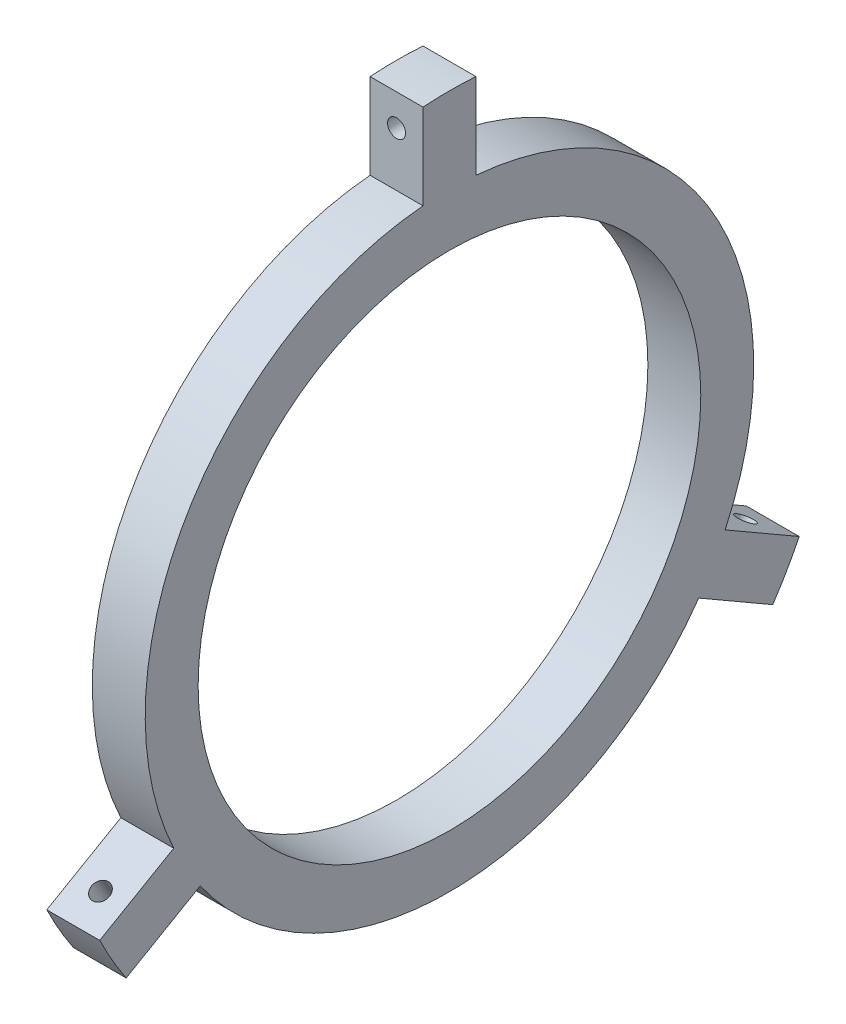
SolidWorks part; units mm, degrees
ref_plane "Plan de face" through (0, 0, 0) normal (0, 0, 1) x (1, 0, 0)
ref_plane "Plan de dessus" through (0, 0, 0) normal (0, 1, 0) x (1, 0, 0)
ref_plane "Plan de droite" through (0, 0, 0) normal (1, 0, 0) x (0, 0, -1)
sketch "Esquisse2" plane through (0, 0, 0) normal (0, 0, 1) x (1, 0, 0)
  line L0 (-5, 0) -> (5, 0)
  line L1 (5, 0) -> (5, 73.61)
  line L2 (5, 73.61) -> (-5, 73.61)
  line L3 (-5, 73.61) -> (-5, 0)
  dimension "D1" = 73.61
  dimension "D2" = 10
extrude "Boss.-Extru.1" add sketch "Esquisse2" along normal blind 5 and the other way blind 5
sketch "Esquisse3" plane through (5, 0, 0) normal (1, 0, 0) x (0, 0, -1)
  line L0 (0, 0) -> (0, 73.61) construction
  line L1 (-25.3992, 69.0892) -> (-25.3992, 83.5877)
  line L2 (-25.3992, 83.5877) -> (25.3992, 83.5877)
  line L3 (25.3992, 83.5877) -> (25.3992, 69.0892)
  line L4 (5, 75) -> (-5, 75) construction
  line L5 (-5, 0) -> (-5, 73.61) construction
  arc A0 (-25.3992, 69.0892) -> (25.3992, 69.0892) centre (0, 0) cw
  dimension "D1" = 73.61
  dimension "D2" = 30.3992
  dimension "D3" = 8.5877
extrude "Enlèv. mat.-Extru.1" cut sketch "Esquisse3" against normal through all
sketch "Esquisse5" plane through (0, 0, 0) normal (0, 1, 0) x (1, 0, 0)
  line L0 (0, 0) -> (7.3012, 0) construction
ref_plane "Plan3" through (0, 0, 0) normal (0, 0, -1) x (-1, 0, 0)
ref_plane "Plan4" through (0, 73.44, 0) normal (0, -1, 0) x (-1, 0, 0)
hole_wizard "Dégagement M31" positions "Esquisse6" profile "Esquisse7" hole size "M3" standard "ISO" end condition through all
sketch "Esquisse6" plane through (0, 0, -5) normal (0, 0, -1) x (-1, 0, 0)
  line L1 (0, 67.5) -> (5, 73.44) construction
  line L3 (0, 67.5) -> (-5, 73.44) construction
  point P35 (0, 67.5)
  dimension "D1" = 67.5
sketch "Esquisse7" plane through (0, 67.5, -5) normal (1, 0, 0) x (0, 1, 0)
  line L0 (0, 0) -> (0, 73.6009)
  line L1 (0, 73.6009) -> (1.7, 73.6009)
  line L2 (1.7, 73.6009) -> (1.7, 0)
  line L5 (1.7, 0) -> (0, 0)
  line L11 (0, -6.35) -> (0, 107.95) construction
  dimension "Diamètre du perçage jusqu'au prochain" = 3.4
  dimension "Profondeur du perçage jusqu'au prochain" = 73.6009
pattern_circular "Répétition circulaire1" count 3 over 360 about axis through (0, 0, 0) along (1, 0, 0) of "Boss.-Extru.1", "Enlèv. mat.-Extru.1", "Dégagement M31" reverse direction yes
ref_plane "Plan1" [suppressed] through (0, 0, 0) normal (0, 0.866, 0.5) x (1, 0, 0)
ref_plane "Plan2" [suppressed] through (0, 0, 0) normal (0, 0.866, -0.5) x (1, 0, 0)
ref_plane "Plan5" [suppressed] through (0, -36.72, 63.6009) normal (0, 0.5, -0.866) x (-1, 0, 0)
ref_plane "Plan6" [suppressed] through (0, -36.72, -63.6009) normal (0, -0.5, -0.866) x (-1, 0, 0)
ref_plane "Plan7" through (0, 0, 0) normal (1, 0, 0) x (0, 0, -1)
sketch "Esquisse8" plane through (5, 0, 0) normal (1, 0, 0) x (0, 0, -1)
  circle A0 centre (0, 0) radius 57.5
  dimension "D1" = 115
extrude "Boss.-Extru.2" add sketch "Esquisse8" against normal up to surface (10 mm away) up to face at (-5, 0, 0)
sketch "Esquisse9" plane through (5, 0, 0) normal (1, 0, 0) x (0, 0, -1)
  circle A0 centre (0, 0) radius 47.5
  arc A1 (52.1078, -24.311) -> (5, 57.2822) centre (0, 0) ccw construction
  dimension "D1" = 10
extrude "Enlèv. mat.-Extru.3" cut sketch "Esquisse9" against normal through all
ref_plane "Plan8" through (0, 0, 0) normal (0, 0.866, -0.5) x (1, 0, 0)
ref_plane "Plan9" through (0, 0, 0) normal (0, 0.866, 0.5) x (1, 0, 0)
